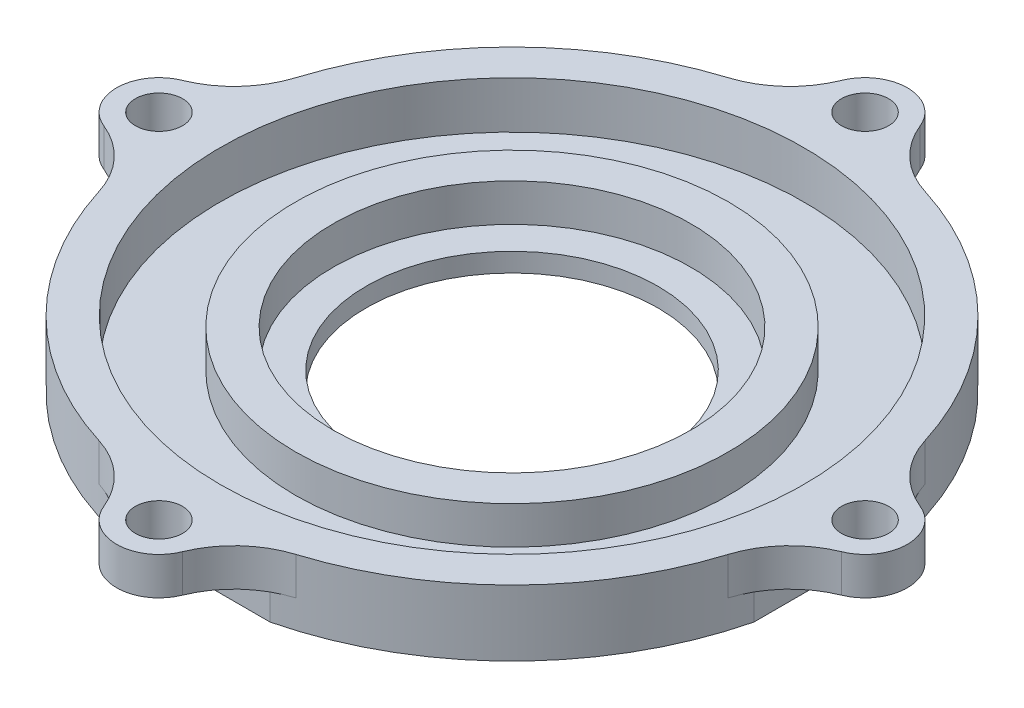
SolidWorks part; units mm, degrees
ref_plane "Front Plane" through (0, 0, 0) normal (0, 0, 1) x (1, 0, 0)
ref_plane "Top Plane" through (0, 0, 0) normal (0, 1, 0) x (1, 0, 0)
ref_plane "Right Plane" through (0, 0, 0) normal (1, 0, 0) x (0, 0, -1)
sketch "Sketch1" plane through (0, 0, 0) normal (0, 1, 0) x (1, 0, 0)
  line L0 (-40, 0) -> (-37.5, 0) construction
  line L1 (-40, 6) -> (-34.4819, 6)
  line L2 (-40, -6) -> (-34.4819, -6)
  line L3 (0, -37.5) -> (0, -40) construction
  line L4 (6, 40) -> (6, 34.4819)
  line L5 (-6, 40) -> (-6, 34.4819)
  line L6 (0, 40) -> (0, 35) construction
  line L13 (-6, -34.4819) -> (-6, -40)
  line L15 (6, -34.4819) -> (6, -40)
  line L16 (34.4819, -6) -> (40, -6)
  line L17 (37.5, 0) -> (40, 0) construction
  line L18 (34.4819, 6) -> (40, 6)
  circle A0 centre (0, 0) radius 31
  arc A1 (-34.4819, -6) -> (-6, -34.4819) centre (0, 0) ccw
  arc A2 (-40, 6) -> (-40, -6) centre (-40, 0) ccw
  arc A3 (40, -6) -> (40, 6) centre (40, 0) ccw
  arc A4 (6, 40) -> (-6, 40) centre (0, 40) ccw
  arc A5 (-6, -40) -> (6, -40) centre (0, -40) ccw
  arc A6 (-39.5474, 6) -> (-40, 0) centre (0, 0) ccw construction
  arc A7 (-6, 39.5474) -> (-39.5474, 6) centre (0, 0) ccw construction
  arc A8 (-40, 0) -> (-39.5474, -6) centre (0, 0) ccw construction
  arc A9 (39.5474, -6) -> (40, 0) centre (0, 0) ccw construction
  arc A10 (-39.5474, -6) -> (-6, -39.5474) centre (0, 0) ccw construction
  arc A11 (-6, -39.5474) -> (0, -40) centre (0, 0) ccw construction
  arc A12 (0, -40) -> (6, -39.5474) centre (0, 0) ccw construction
  arc A13 (6, -39.5474) -> (39.5474, -6) centre (0, 0) ccw construction
  arc A14 (40, 0) -> (39.5474, 6) centre (0, 0) ccw construction
  arc A15 (0, 40) -> (-6, 39.5474) centre (0, 0) ccw construction
  arc A16 (39.5474, 6) -> (6, 39.5474) centre (0, 0) ccw construction
  arc A17 (6, 39.5474) -> (0, 40) centre (0, 0) ccw construction
  circle A18 centre (-40, 0) radius 2.5
  circle A19 centre (0, 40) radius 2.5
  circle A20 centre (40, 0) radius 2.5
  circle A21 centre (0, -40) radius 2.5
  arc A22 (34.4819, 6) -> (6, 34.4819) centre (0, 0) ccw
  arc A23 (-6, 34.4819) -> (-34.4819, 6) centre (0, 0) ccw
  arc A24 (6, -34.4819) -> (34.4819, -6) centre (0, 0) ccw
  point P6 (0, 0)
  point P11 (0, 0)
  point P53 (0, 0)
  dimension "D1" = 4
  dimension "D2" = 70
  dimension "D5" = 6
  dimension "D6" = 6
  dimension "D7" = 5
  dimension "D3" = 80
  dimension "D4" = 80
  dimension "D8" = 4
extrude "Boss-Extrude1" add sketch "Sketch1" along normal blind 3
sketch "Sketch2" plane through (0, 0, 0) normal (0, 1, 0) x (1, 0, 0)
  circle A0 centre (0, 0) radius 35
  circle A1 centre (0, 0) radius 31
extrude "Boss-Extrude3" add sketch "Sketch2" against normal blind 2
sketch "Sketch3" plane through (0, -2, 0) normal (0, -1, 0) x (1, 0, 0)
  circle A0 centre (0, 0) radius 35
  circle A1 centre (0, 0) radius 15.5
  dimension "D1" = 31
extrude "Boss-Extrude4" add sketch "Sketch3" along normal blind 2
sketch "Sketch4" plane through (0, -2, 0) normal (0, 1, 0) x (1, 0, 0)
  circle A1 centre (0, 0) radius 19
  circle A2 centre (0, 0) radius 23
  dimension "D1" = 38
  dimension "D2" = 4
extrude "Boss-Extrude5" add sketch "Sketch4" along normal blind 4
sketch "Sketch5" plane through (0, -4, 0) normal (0, -1, 0) x (1, 0, 0)
  circle A0 centre (0, 0) radius 35
  circle A1 centre (0, 0) radius 57.3971
extrude "Cut-Extrude1" cut sketch "Sketch5" against normal through all
sketch "Sketch6" plane through (0, 3, 0) normal (0, 1, 0) x (1, 0, 0)
  line L0 (-37.5, 0) -> (-37.5, 2.5)
  line L1 (-37.5, -4.5) -> (-33.5, -4.5)
  line L2 (-37.5, 4.5) -> (-33.5, 4.5)
  line L3 (-33.5, -4.5) -> (-33.5, 4.5)
  line L4 (-4.5, 37.5) -> (-4.5, 33.5)
  line L5 (4.5, 37.5) -> (4.5, 33.5)
  line L6 (-4.5, 33.5) -> (4.5, 33.5)
  line L7 (37.5, 4.5) -> (33.5, 4.5)
  line L8 (37.5, -4.5) -> (33.5, -4.5)
  line L9 (33.5, 4.5) -> (33.5, -4.5)
  line L10 (4.5, -37.5) -> (4.5, -33.5)
  line L11 (-4.5, -37.5) -> (-4.5, -33.5)
  line L12 (4.5, -33.5) -> (-4.5, -33.5)
  circle A0 centre (0, 0) radius 37.5 construction
  circle A1 centre (-37.5, 0) radius 2.5
  circle A2 centre (0, 0) radius 35 construction
  arc A3 (-37.23, 4.4919) -> (-37.23, -4.4919) centre (-37.5, 0) ccw
  circle A4 centre (0, 37.5) radius 2.5
  arc A5 (4.4919, 37.23) -> (-4.4919, 37.23) centre (0, 37.5) ccw
  circle A6 centre (37.5, 0) radius 2.5
  arc A7 (37.23, -4.4919) -> (37.23, 4.4919) centre (37.5, 0) ccw
  circle A8 centre (0, -37.5) radius 2.5
  arc A9 (-4.4919, -37.23) -> (4.4919, -37.23) centre (0, -37.5) ccw
  point P41 (0, 0)
  circle M2 centre (0, 0) radius 35
  dimension "D1" = 5
  dimension "D2" = 2
  dimension "D3" = 4
extrude "Boss-Extrude6" add sketch "Sketch6" against normal blind 4 contours L2 A3 L1 A1 M2 | L1 L3 L2 M2 | L4 L6 L5 M2 | L5 A5 L4 A4 M2 | A7 L7 A6 L8 M2 | L7 L9 L8 M2 | L10 L12 L11 M2 | L11 A9 L10 A8 M2 region at (-41.8842, 3, 0) region at (-34.2043, 3, 0) region at (-2.2621, 3, 35.0429) region at (0, 3, 34.2043) region at (0, 3, -34.2043) region at (-4.3842, 3, -36.1048) region at (35.0429, 3, 2.2621) region at (34.2043, 3, 0)
fillet "Fillet1" radius 10 8 edges at (-34.7095, 1, -4.5) (-4.5, 1, -34.7095) (4.5, 1, -34.7095) (34.7095, 1, -4.5) (34.7095, 1, 4.5) (4.5, 1, 34.7095) (-4.5, 1, 34.7095) (-34.7095, 1, 4.5)
sketch "Sketch7" plane through (0, -4, 0) normal (0, -1, 0) x (1, 0, 0)
  line L1 (-8.3066, -34) -> (8.3066, -34)
  line L2 (-34, -8.3066) -> (-34, 8.3066)
  line L3 (-8.3066, 34) -> (8.3066, 34)
  line L4 (34, -8.3066) -> (34, 8.3066)
  arc A0 (-8.3066, -34) -> (8.3066, -34) centre (0, 0) ccw
  arc A1 (34, -8.3066) -> (34, 8.3066) centre (0, 0) ccw
  arc A2 (8.3066, 34) -> (-8.3066, 34) centre (0, 0) ccw
  arc A3 (-34, 8.3066) -> (-34, -8.3066) centre (0, 0) ccw
  dimension "D3" = 70
extrude "Cut-Extrude2" cut sketch "Sketch7" against normal up to surface (3 mm away) up to face at (-36.6469, -1, 0.4167)
